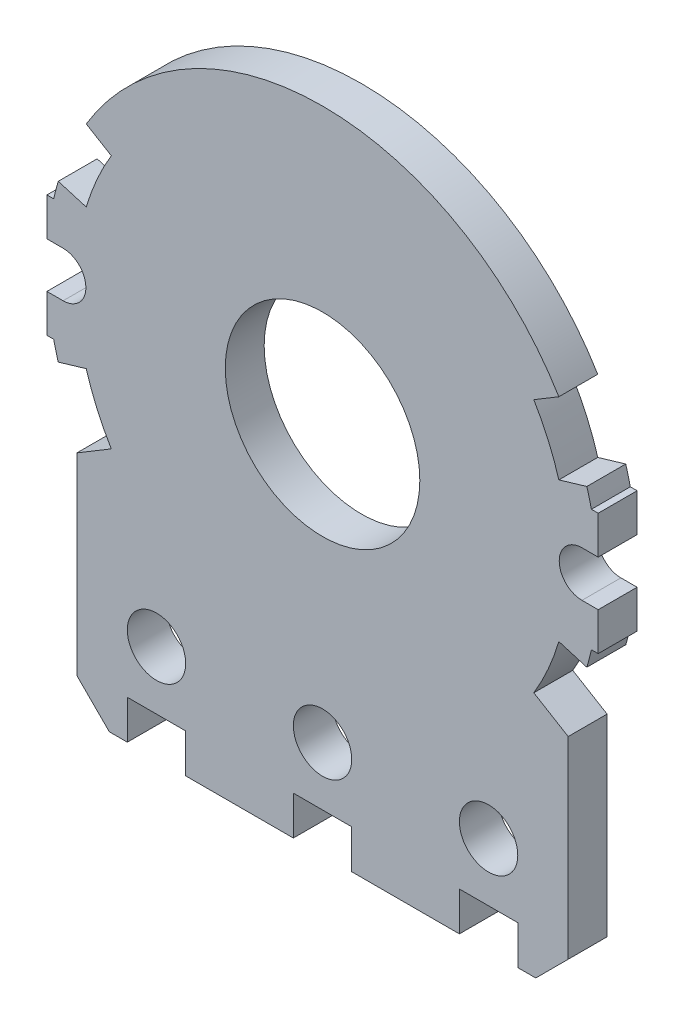
SolidWorks part; units mm, degrees
material "ABS"
ref_plane "Front" through (0, 0, 0) normal (0, 0, 1) x (1, 0, 0)
ref_plane "Top" through (0, 0, 0) normal (0, 1, 0) x (1, 0, 0)
ref_plane "Right" through (0, 0, 0) normal (1, 0, 0) x (0, 0, -1)
sketch "Sketch1" plane through (0, 0, 0) normal (0, 0, 1) x (1, 0, 0)
  line L0 (0, 0) -> (0, -7.678) construction
  line L1 (0, 8.5) -> (13.6887, 8.5) construction
  line L2 (-7.575, -11.5) -> (7.575, -11.5)
  line L3 (-7.575, -11.5) -> (-7.575, -3.8561)
  line L4 (-7.575, -3.8561) -> (7.575, -3.8561)
  line L5 (7.575, -11.5) -> (7.575, -3.8561)
  line L6 (-7.575, -11.5) -> (7.575, -3.8561) construction
  line L7 (-7.575, -3.8561) -> (7.575, -11.5) construction
  line L8 (13.6887, 8.5) -> (13.6887, -11.5) construction
  line L9 (13.6887, -11.5) -> (7.575, -11.5) construction
  line L11 (-8.5, -1.875) -> (8.5, -1.875)
  line L12 (-8.5, -1.875) -> (-8.5, 1.875)
  line L13 (-8.5, 1.875) -> (8.5, 1.875)
  line L14 (8.5, -1.875) -> (8.5, 1.875)
  line L15 (-8.5, -1.875) -> (8.5, 1.875) construction
  line L16 (-8.5, 1.875) -> (8.5, -1.875) construction
  circle A0 centre (0, 0) radius 8.5
  circle A1 centre (0, 0) radius 3
extrude "Boss-Extrude1" add sketch "Sketch1" along normal blind 1.2 contours A1 L4 A0 | A1 L4 A0 | A0 L3 L2 L5 | A1 L13 A0 L11 | A0 L12 L11 | A0 L13 L12 | A1 L13 A0 | A1 L11 A0 L13 | A0 L14 L13 | A0 L11 L14 region at (0, -9.1446, 0) region at (-7.8374, -2.8311, 0) region at (0, -5.7654, 0) region at (-5.608, 0, 0) region at (-8.4373, -1.4074, 0) region at (8.4373, -1.4074, 0) region at (5.608, 0, 0) region at (-8.4373, 1.4074, 0) region at (8.4373, 1.4074, 0) region at (0, 4.7482, 0)
sketch "Sketch2" plane through (0, 0, 1.2) normal (0, 0, 1) x (1, 0, 0)
  line L0 (0, 0) -> (0, -11.5) construction
  line L1 (-7.575, -11.5) -> (7.575, -11.5) construction
  line L2 (4.22, -10.3) -> (6.02, -10.3)
  line L3 (-0.9, -10.3) -> (0.9, -10.3)
  line L4 (-0.9, -10.3) -> (-0.9, -11.5)
  line L5 (-0.9, -11.5) -> (0.9, -11.5)
  line L6 (0.9, -10.3) -> (0.9, -11.5)
  line L7 (-0.9, -10.3) -> (0.9, -11.5) construction
  line L8 (-0.9, -11.5) -> (0.9, -10.3) construction
  line L9 (4.22, -10.3) -> (4.22, -11.5)
  line L10 (4.22, -11.5) -> (6.02, -11.5)
  line L11 (6.02, -10.3) -> (6.02, -11.5)
  line L12 (-6.02, -10.3) -> (-6.02, -11.5)
  line L13 (-4.22, -11.5) -> (-6.02, -11.5)
  line L14 (-4.22, -10.3) -> (-4.22, -11.5)
  line L15 (-4.22, -10.3) -> (-6.02, -10.3)
  line L16 (7.575, -11.5) -> (7.575, -10.5)
  line L17 (7.575, -11.5) -> (7.575, -3.8561) construction
  line L18 (7.575, -10.5) -> (6.575, -11.5)
  line L19 (6.575, -11.5) -> (7.575, -11.5)
  line L20 (6.02, -10.3) -> (7.575, -10.3) construction
  line L21 (-6.575, -11.5) -> (-7.575, -11.5)
  line L22 (-7.575, -10.5) -> (-6.575, -11.5)
  line L23 (-7.575, -11.5) -> (-7.575, -10.5)
  line L24 (2.6771, -11.5) -> (2.6771, -8.5) construction
  line L25 (2.6771, -8.5) -> (5.12, -8.5) construction
  circle A0 centre (0, -8.5) radius 0.9
  circle A1 centre (5.12, -8.5) radius 0.9
  circle A2 centre (-5.12, -8.5) radius 0.9
  circle A3 centre (0, 0) radius 7.6 construction
  point P5 (0, -10.9)
  dimension "D2" = 2
  dimension "D1" = 2
extrude "Cut-Extrude1" cut sketch "Sketch2" against normal through all
sketch "Sketch3" plane through (0, 0, 1.2) normal (0, 0, 1) x (1, 0, 0)
  line L0 (0, 0) -> (8.5, 0) construction
  line L1 (7.287, 2.1585) -> (9.1197, 2.7014)
  line L2 (0, 0) -> (6.5145, 3.9143) construction
  line L3 (6.5145, 3.9143) -> (8.0188, 4.8182)
  line L4 (8.0188, 4.8182) -> (9.1197, 2.7014)
  line L5 (8.0188, -4.8182) -> (9.1197, -2.7014)
  line L6 (6.5145, -3.9143) -> (8.0188, -4.8182)
  line L7 (7.287, -2.1585) -> (9.1197, -2.7014)
  line L8 (0, 8.5) -> (0, 0) construction
  line L9 (-7.287, -2.1585) -> (-9.1197, -2.7014)
  line L10 (-6.5145, -3.9143) -> (-8.0188, -4.8182)
  line L11 (-8.0188, -4.8182) -> (-9.1197, -2.7014)
  line L12 (-8.0188, 4.8182) -> (-9.1197, 2.7014)
  line L13 (-6.5145, 3.9143) -> (-8.0188, 4.8182)
  line L14 (-7.287, 2.1585) -> (-9.1197, 2.7014)
  line L15 (0, 0) -> (7.287, 2.1585) construction
  line L16 (-9, -0.7017) -> (-8, -0.7017)
  line L17 (-9, -0.7017) -> (-9, 0.7017)
  line L18 (-9, 0.7017) -> (-8, 0.7017)
  line L19 (-8, -0.7017) -> (-8, 0.7017)
  line L20 (-9, -0.7017) -> (-8, 0.7017) construction
  line L21 (-9, 0.7017) -> (-8, -0.7017) construction
  line L22 (9, -0.7017) -> (8, -0.7017)
  line L23 (9, -0.7017) -> (9, 0.7017)
  line L24 (9, 0.7017) -> (8, 0.7017)
  line L25 (8, -0.7017) -> (8, 0.7017)
  line L26 (9, -0.7017) -> (8, 0.7017) construction
  line L27 (9, 0.7017) -> (8, -0.7017) construction
  arc A0 (7.575, -3.8561) -> (8.2906, -1.875) centre (0, 0) ccw construction
  circle A1 centre (8, 0) radius 0.7017
  arc A2 (6.5145, 3.9143) -> (7.287, 2.1585) centre (0, 0) cw
  arc A3 (6.5145, -3.9143) -> (7.287, -2.1585) centre (0, 0) ccw
  arc A4 (-6.5145, -3.9143) -> (-7.287, -2.1585) centre (0, 0) cw
  arc A5 (-6.5145, 3.9143) -> (-7.287, 2.1585) centre (0, 0) ccw
  circle A6 centre (-8, 0) radius 0.7017
  point P26 (-8.5, 0)
  line M17 (7.575, -10.5) -> (7.575, -3.8561)
  arc M18 (7.575, -3.8561) -> (8.2906, -1.875) centre (0, 0) ccw
  line M19 (-7.575, -3.8561) -> (-7.575, -10.5)
extrude "Cut-Extrude2" cut sketch "Sketch3" against normal blind 10 contours L25 A1 | A1 L25 M18 | A1 L24 M18 | A1 L22 M18 | A1 L22 L23 L24 M18 | A1 M18 | A6 L19 M18 | A6 M18 | A6 L18 L17 L16 M18 | A6 L18 M18 | L16 A6 M18 | A6 L19 | A5 L13 L14 M18 | L10 A4 L9 M18 M19 | L11 L10 L9 M19 M18 | L14 L13 L12 M18 | L7 L6 L5 M18 M17 | A3 L6 L7 M17 M18 | L4 L3 L1 M18 | L3 A2 L1 M18 region at (7.788, 3.4059, 1.2) region at (8.221, -3.5247, 1.2) region at (7.3626, -3.2892, 1.2) region at (-7.788, -3.4059, 1.2) region at (-7.788, 3.4059, 1.2) region at (-8.7482, 0, 1.2) region at (-8.2978, 0, 1.2) region at (-7.7022, 0, 1.2) region at (8.7482, 0, 1.2) region at (7.7022, 0, 1.2) region at (8.2978, 0, 1.2)
